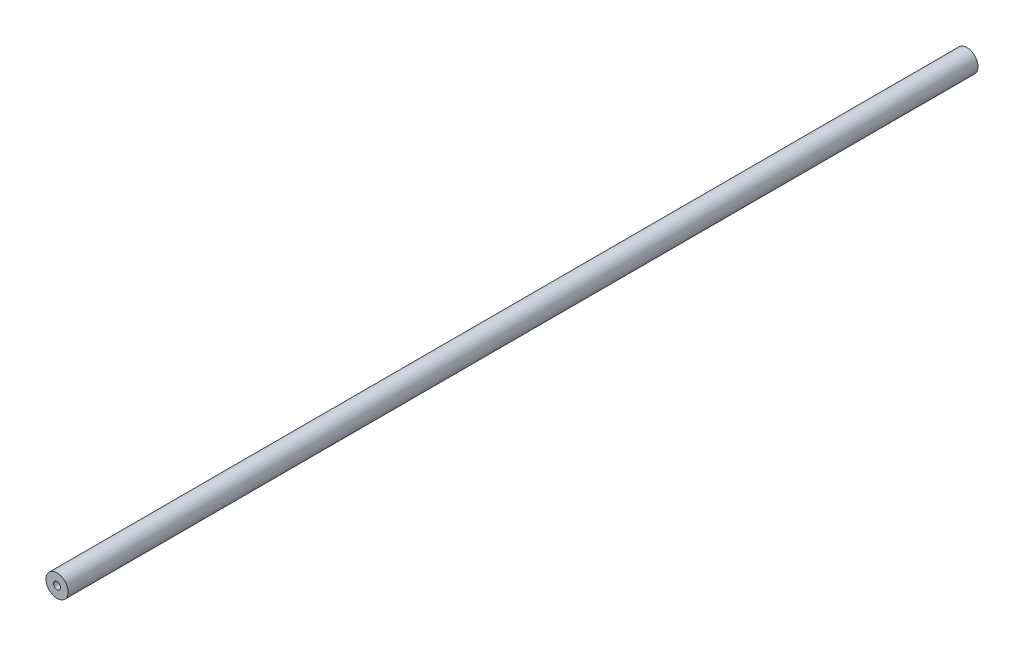
SolidWorks part; units mm, degrees
material "6061-T6 (SS)"
ref_plane "Front Plane" through (0, 0, 0) normal (0, 0, 1) x (1, 0, 0)
ref_plane "Top Plane" through (0, 0, 0) normal (0, 1, 0) x (1, 0, 0)
ref_plane "Right Plane" through (0, 0, 0) normal (1, 0, 0) x (0, 0, -1)
sketch "Sketch1" plane through (0, 0, 0) normal (0, 0, 1) x (1, 0, 0)
  circle A0 centre (0, 0) radius 6.35
  dimension "D1" = 12.7
extrude "Boss-Extrude1" add sketch "Sketch1" along normal blind 521.208
hole_wizard "#10-32 Tapped Hole1" positions "Sketch3" profile "Sketch2" tap size "#10-32" standard "ANSI Inch"
sketch "Sketch3" plane through (0, 0, 521.208) normal (0, 0, 1) x (1, 0, 0)
  point P0 (0, 0)
sketch "Sketch2" plane through (0, 0, 521.208) normal (1, 0, 0) x (0, -1, 0)
  line L0 (0, 0) -> (0, 14.9293)
  line L1 (0, 14.9293) -> (2.0193, 13.716)
  line L2 (2.0193, 13.716) -> (2.0193, 0)
  line L5 (2.0193, 0) -> (0, 0)
  line L10 (0, 14.9293) -> (-2.0193, 13.716) construction
  line L11 (0, -6.35) -> (0, 107.95) construction
  dimension "Tap Drill Dia." = 4.0386
  dimension "Tap Drill Depth" = 13.716
  dimension "Drill Angle" = 118
cosmetic thread "Hole Thread1"
hole_wizard "#10-32 Tapped Hole2" positions "Sketch5" profile "Sketch4" tap size "#10-32" standard "ANSI Inch"
sketch "Sketch5" plane through (0, 0, 0) normal (0, 0, -1) x (-1, 0, 0)
  point P0 (0, 0)
sketch "Sketch4" plane through (0, 0, 0) normal (1, 0, 0) x (0, 1, 0)
  line L0 (0, 0) -> (0, 14.9293)
  line L1 (0, 14.9293) -> (2.0193, 13.716)
  line L2 (2.0193, 13.716) -> (2.0193, 0)
  line L5 (2.0193, 0) -> (0, 0)
  line L10 (0, 14.9293) -> (-2.0193, 13.716) construction
  line L11 (0, -6.35) -> (0, 107.95) construction
  dimension "Tap Drill Dia." = 4.0386
  dimension "Tap Drill Depth" = 13.716
  dimension "Drill Angle" = 118
cosmetic thread "Hole Thread2" parameters "D1"=9.652, "D2"=4.826
